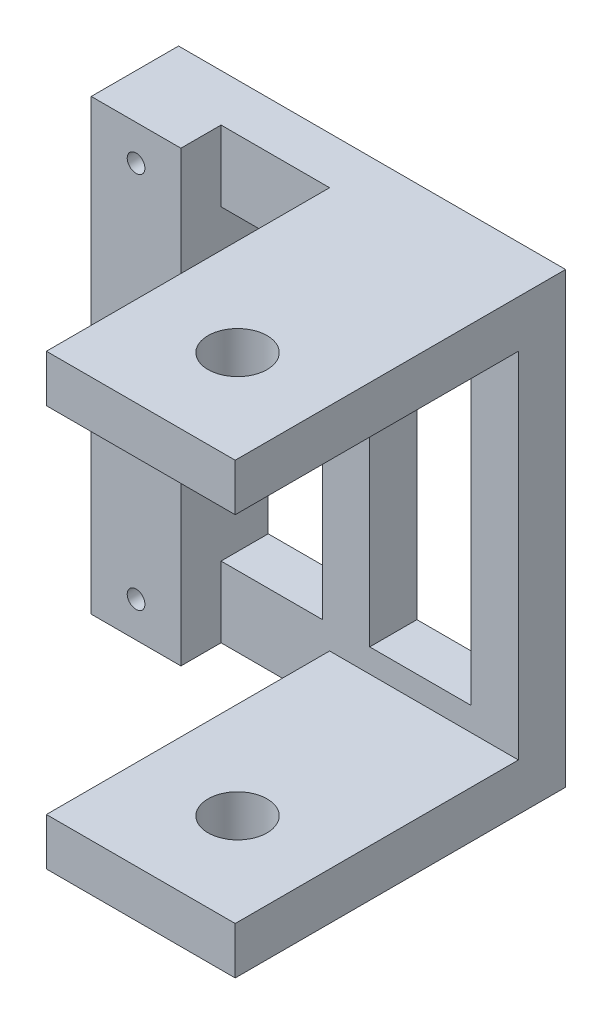
SolidWorks part; units mm, degrees
ref_plane "前视基准面" through (0, 0, 0) normal (0, 0, 1) x (1, 0, 0)
ref_plane "上视基准面" through (0, 0, 0) normal (0, 1, 0) x (1, 0, 0)
ref_plane "右视基准面" through (0, 0, 0) normal (1, 0, 0) x (0, 0, -1)
sketch "草图2" plane through (0, 0, 0) normal (0, 0, 1) x (1, 0, 0)
  line L3 (-9.1, -9.5) -> (7.3, -9.5)
  line L4 (7.3, 9.5) -> (7.3, -9.5)
  line L5 (0, 0) -> (2.4933, 0) construction
  line L6 (0, 0) -> (0, -3.9686) construction
  line L15 (-9.1, 9.5) -> (7.3, 9.5)
  line L16 (-5.3, 6.5) -> (-1, 6.5)
  line L17 (-5.3, 6.5) -> (-5.3, -6.5)
  line L18 (-5.3, -6.5) -> (-1, -6.5)
  line L20 (-9.1, 9.5) -> (-9.1, -9.5)
  line L21 (1, 6.5) -> (5.3, 6.5)
  line L23 (1, -6.5) -> (1, 6.5)
  line L25 (-1, -6.5) -> (-1, 6.5)
  line L26 (5.3, 6.5) -> (5.3, -6.5)
  line L28 (1, -6.5) -> (5.3, -6.5)
  point P0 (0, 0)
  dimension "D1" = 16.4
  dimension "D3" = 19
  dimension "D4" = 3.8
  dimension "D5" = 3
  dimension "D6" = 2
  dimension "D8" = 3
  dimension "D9" = 2
extrude "凸台-拉伸1" add sketch "草图2" along normal blind 2
sketch "草图3" plane through (0, 0, 2) normal (0, 0, 1) x (1, 0, 0)
  line L1 (-0.7, 9.5) -> (7.3, 9.5)
  line L2 (-0.7, 9.5) -> (-0.7, 7.5)
  line L3 (-0.7, 7.5) -> (7.3, 7.5)
  line L4 (7.3, 9.5) -> (7.3, 7.5)
  line L5 (7.3, -9.5) -> (7.3, 9.5) construction
  line L6 (-0.7, -7.5) -> (7.3, -7.5)
  line L8 (-0.7, -9.5) -> (7.3, -9.5)
  line L9 (7.3, -7.5) -> (7.3, -9.5)
  line L10 (-9.1, -9.5) -> (7.3, -9.5) construction
  line L11 (-0.7, -7.5) -> (-0.7, -9.5)
  line L12 (7.3, 9.5) -> (-9.1, 9.5) construction
  dimension "D1" = 2
  dimension "D2" = 2
  dimension "D3" = 8
  dimension "D4" = 8
extrude "凸台-拉伸2" add sketch "草图3" along normal blind 12
sketch "草图10" plane through (0, 0, 2) normal (0, 0, 1) x (1, 0, 0)
  line L0 (-9.1, 9.5) -> (-9.1, -9.5) construction
  line L1 (-9.1, 9.5) -> (-5.3, 9.5)
  line L2 (-9.1, 9.5) -> (-9.1, -9.5)
  line L3 (-9.1, -9.5) -> (-5.3, -9.5)
  line L4 (-5.3, 9.5) -> (-5.3, -9.5)
  line L5 (-0.7, 9.5) -> (-9.1, 9.5) construction
  line L6 (-9.1, -9.5) -> (-0.7, -9.5) construction
  line L7 (-5.3, 6.5) -> (-5.3, -6.5) construction
extrude "凸台-拉伸4" add sketch "草图10" along normal blind 1.7
sketch "草图9" plane through (0, 0, 2) normal (0, 0, 1) x (1, 0, 0)
  line L0 (-0.7, 9.5) -> (-5.3, 9.5) construction
  line L1 (-9.1, 9.5) -> (-9.1, -9.5) construction
  line L2 (-5.3, -9.5) -> (-0.7, -9.5) construction
  circle A0 centre (-7.2, 8) radius 0.375
  circle A1 centre (-7.2, -8) radius 0.375
  dimension "D1" = 0.75
  dimension "D2" = 0.75
  dimension "D3" = 1.5
  dimension "D4" = 1.9
  dimension "D5" = 1.5
  dimension "D6" = 1.9
extrude "切除-拉伸2" cut sketch "草图9" against normal up to next from surface starting at face at (-7.2, 0, 3.7)
sketch "草图11" plane through (0, -9.5, 0) normal (0, -1, 0) x (1, 0, 0)
  circle A0 centre (3.4, 10) radius 1.25
  dimension "D1" = 2.5
extrude "切除-拉伸3" cut sketch "草图11" against normal through all
